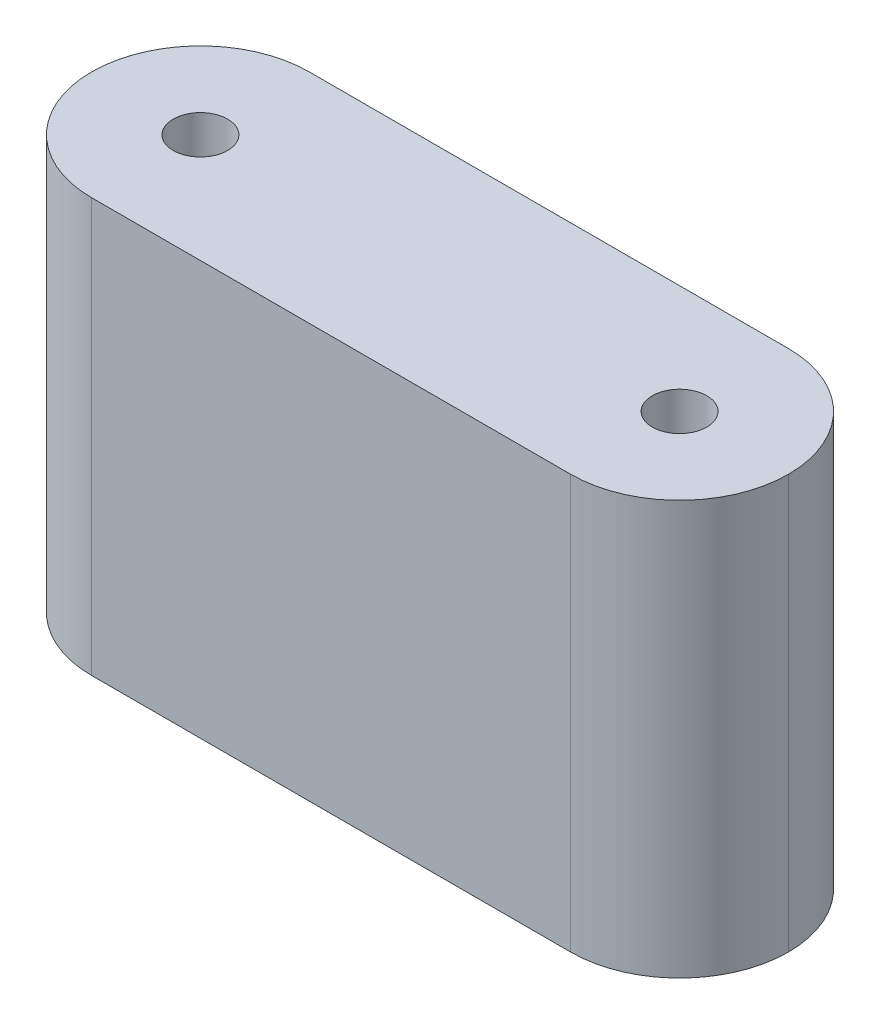
SolidWorks part; units mm, degrees
ref_plane "前视基准面" through (0, 0, 0) normal (0, 0, 1) x (1, 0, 0)
ref_plane "上视基准面" through (0, 0, 0) normal (0, 1, 0) x (1, 0, 0)
ref_plane "右视基准面" through (0, 0, 0) normal (1, 0, 0) x (0, 0, -1)
sketch "草图1" plane through (0, 0, 0) normal (0, 1, 0) x (1, 0, 0)
  line L0 (16, 10) -> (16, 0)
  line L1 (0, 0) -> (32, 0)
  line L2 (0, 0) -> (0, 10)
  line L3 (0, 10) -> (32, 10)
  line L4 (32, 0) -> (32, 10)
  line L5 (16, 5) -> (5, 5)
  circle A0 centre (5, 5) radius 1.25
  circle A1 centre (27, 5) radius 1.25
extrude "凸台-拉伸1" add sketch "草图1" along normal blind 18 contours L1 L4 L3 L0 A1 | A0 L0 L3 L2 L1 region at (23.905, 0, -5) region at (15.8113, 0, -7.5)
sketch "草图4" plane through (0, 18, 0) normal (0, 1, 0) x (1, 0, 0)
  line L1 (0, 0) -> (32, 0)
  line L2 (0, 0) -> (0, 10)
  line L3 (0, 10) -> (32, 10)
  line L4 (32, 0) -> (32, 10)
  circle A0 centre (5, 5) radius 1.25
  circle A1 centre (27, 5) radius 1.25
extrude "凸台-拉伸3" add sketch "草图4" along normal blind 1
fillet "圆角3" radius 5 1 edges at (0, 9.5, -10)
fillet "圆角4" radius 5 3 edges at (32, 9.5, -10) (32, 9.5, 0) (0, 9.5, 0)
